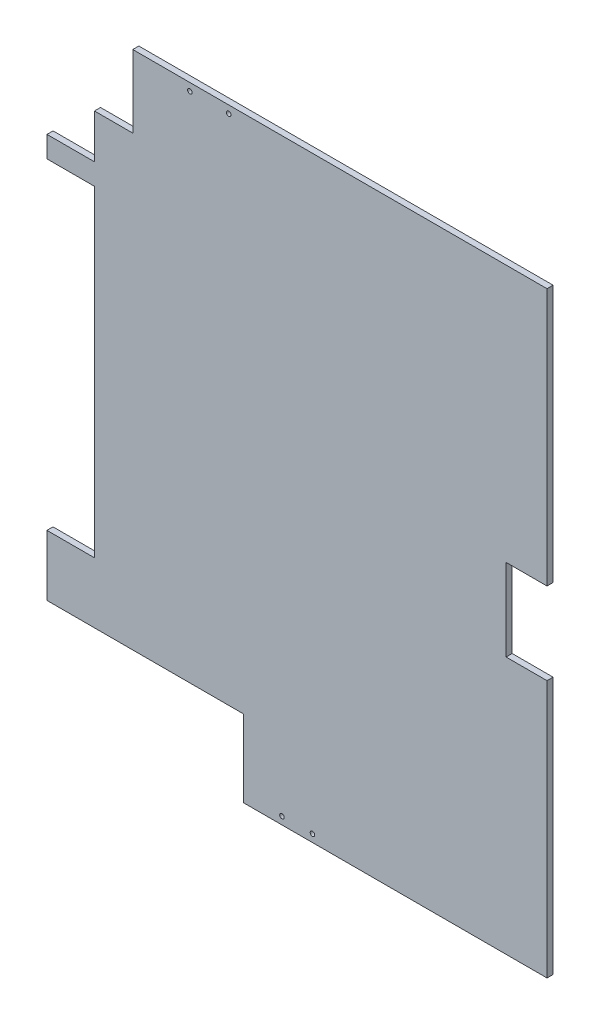
SolidWorks part; units mm, degrees
material "Balsa"
ref_plane "Front Plane" through (0, 0, 0) normal (0, 0, 1) x (1, 0, 0)
ref_plane "Top Plane" through (0, 0, 0) normal (0, 1, 0) x (1, 0, 0)
ref_plane "Right Plane" through (0, 0, 0) normal (1, 0, 0) x (0, 0, -1)
sketch "Sketch1" plane through (0, 0, 0) normal (0, 0, 1) x (1, 0, 0)
  line L0 (-5.7823, -13) -> (25.5, -13)
  line L2 (-5.7823, 1) -> (-5.7823, -13)
  line L5 (24.5, -14) -> (-24.5, -14) construction
  line L6 (323.7481, -265) -> (323.7481, 30)
  line L7 (-5.8246, -265) -> (65.6329, -265)
  line L8 (-5.8246, -265) -> (-5.8246, -225)
  line L11 (-5.8246, -265) -> (65.6329, -225) construction
  line L12 (-5.8246, -225) -> (65.6329, -265) construction
  line L15 (323.7481, -265) -> (25.5, -265)
  line L16 (25.5, 1) -> (25.5, -265)
  line L17 (-5.8246, -225) -> (25.5, -225)
  line L18 (-24.5, -224) -> (24.5, -224) construction
  line L19 (-5.7823, 1) -> (25.5, 1)
  line L20 (24.5, -224) -> (24.5, -14) construction
  line L21 (-85.1981, 31) -> (50.7481, 31) construction
  line L23 (25.5, 1) -> (25.5, 30)
  line L24 (25.5, 30) -> (323.7481, 30)
  line L27 (277.3251, 57) -> (277.3251, -295) construction
  line L28 (26.2777, -266) -> (-26.2882, -266) construction
  line L30 (-63.4467, 81) -> (255.5737, 81) construction
  line L31 (50.7481, 30) -> (323.7481, 30)
  line L32 (50.7481, 30) -> (50.7481, 77.7)
  line L33 (50.7481, 77.7) -> (323.7481, 77.7)
  line L34 (323.7481, 30) -> (323.7481, 77.7)
  line L35 (50.7481, 30) -> (323.7481, 77.7) construction
  line L36 (50.7481, 77.7) -> (323.7481, 30) construction
  line L37 (255.5737, -319) -> (-63.4467, -319) construction
  line L38 (323.7481, -265) -> (123.7481, -265)
  line L39 (323.7481, -265) -> (323.7481, -315.7)
  line L40 (323.7481, -315.7) -> (123.7481, -315.7)
  line L41 (123.7481, -265) -> (123.7481, -315.7)
  line L42 (323.7481, -265) -> (123.7481, -315.7) construction
  line L43 (323.7481, -315.7) -> (123.7481, -265) construction
  line L44 (50.7481, 31) -> (50.7481, -269) construction
  point P4 (32.4695, -6)
  point P10 (29.9042, -245)
  point P15 (48.1318, -132)
  point P24 (48.1318, 15.5)
  point P36 (187.2481, 53.85)
  point P42 (223.7481, -290.35)
  dimension "D1" = 1
  dimension "D2" = 1
  dimension "D3" = 1
  dimension "D4" = 1
  dimension "D5" = 1
  dimension "D6" = 31.3246
  dimension "D7" = 273
  dimension "D8" = 3.3
  dimension "D9" = 200
  dimension "D10" = 3.3
extrude "Boss-Extrude1" add sketch "Sketch1" along normal blind 4 contours L24 L23 L16 L7 L15 L6 | L19 L2 L0 L16 | L17 L8 L7 L16 | L24 L34 L33 L32 | L15 L41 L40 L39 region at (9.8589, -6, 0) region at (174.6241, -117.5, 0) region at (9.8377, -245, 0) region at (187.2481, 53.85, 0) region at (223.7481, -290.35, 0)
sketch "Sketch2" plane through (0, 0, 0) normal (0, 0, -1) x (-1, 0, 0)
  circle A0 centre (-113.9984, 72.7) radius 1.5
  circle A1 centre (-88.397, 72.7) radius 1.5
  circle A2 centre (-169.1689, -310.7) radius 1.5
  circle A3 centre (-149.0844, -310.7) radius 1.5
  dimension "D1" = 3
  dimension "D2" = 3
  dimension "D3" = 3
  dimension "D4" = 3
extrude "Cut-Extrude1" cut sketch "Sketch2" against normal through all
sketch "Sketch3" plane through (119.3915, 0, 256.0358) normal (0.4226, 0, 0.9063) x (0.9063, 0, -0.4226)
  line L1 (293.4595, -146) -> (268.9595, -146)
  line L2 (293.4595, -146) -> (293.4595, -92)
  line L3 (293.4595, -92) -> (268.9595, -92)
  line L4 (268.9595, -146) -> (268.9595, -92)
  line L5 (293.4595, -146) -> (268.9595, -92) construction
  line L6 (293.4595, -92) -> (268.9595, -146) construction
  point P4 (281.2095, -119)
extrude "Cut-Extrude2" cut sketch "Sketch3" against normal through all both and the other way through all
sketch "Sketch4" plane through (0, 0, 0) normal (0, 0, -1) x (-1, 0, 0)
  line L1 (-323.7481, -92) -> (-296.7639, -92)
  line L2 (-323.7481, -92) -> (-323.7481, -146)
  line L3 (-323.7481, -146) -> (-296.7639, -146)
  line L4 (-296.7639, -92) -> (-296.7639, -146)
  line L5 (-323.7481, -92) -> (-296.7639, -146) construction
  line L6 (-323.7481, -146) -> (-296.7639, -92) construction
  point P4 (-310.256, -119)
extrude "Cut-Extrude3" cut sketch "Sketch4" against normal blind 10
